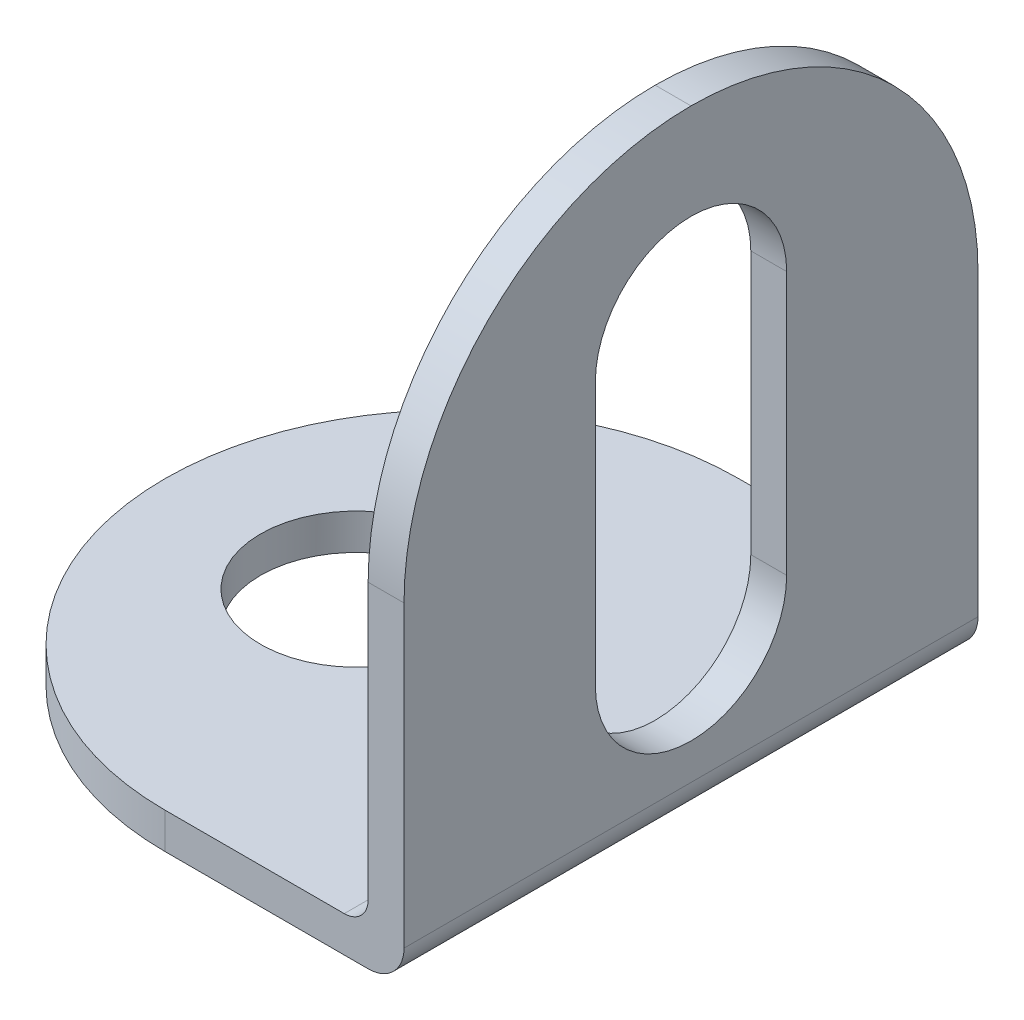
SolidWorks part; units mm, degrees
ref_plane "Piano frontale" through (0, 0, 0) normal (0, 0, 1) x (1, 0, 0)
ref_plane "Piano superiore" through (0, 0, 0) normal (0, 1, 0) x (1, 0, 0)
ref_plane "Piano destro" through (0, 0, 0) normal (1, 0, 0) x (0, 0, -1)
sketch "Schizzo1" plane through (0, 0, 0) normal (0, 0, 1) x (1, 0, 0)
  line L0 (0, 13) -> (0, 0)
  line L1 (0, 0) -> (-11, 0)
  dimension "D1" = 13
  dimension "D2" = 11
extrude "Estrusione-Sottile1" add sketch "Schizzo1" along normal mid plane 12 thin contours L0 L1 thin type one direction wall 0.75
fillet "Raccordo3" radius 6 4 edges at (-11, 0.375, 6) (-11, 0.375, -6) (-0.375, 13, -6) (-0.375, 13, 6)
sketch "Schizzo4" plane through (0, 0.75, 0) normal (0, 1, 0) x (1, 0, 0)
  circle A2 centre (-7, 0) radius 2
  point P0 (-5.8105, -0.1666)
  dimension "D1" = 4
  dimension "D2" = 4
extrude "Taglio-Estrusione1" cut sketch "Schizzo4" against normal up to surface (0.75 mm away) up to face at (-4.6971, 0, 0)
sketch "Schizzo5" plane through (-0.75, 0, 0) normal (-1, 0, 0) x (0, 0, 1)
  line L0 (0, 9) -> (0, 3.5) construction
  line L1 (2, 9) -> (2, 3.5)
  line L2 (-2, 9) -> (-2, 3.5)
  arc A0 (2, 9) -> (-2, 9) centre (0, 9) ccw
  arc A1 (-2, 3.5) -> (2, 3.5) centre (0, 3.5) ccw
  point P3 (0, 6.25)
  point P9 (0, 11)
  point P10 (0, 4.3327)
  point P11 (0, 1.5)
  dimension "D1" = 2
  dimension "D2" = 2
  dimension "D3" = 1.5
fillet "Raccordo1" radius 0.75 1 edges at (0, 0, 0)
fillet "Raccordo2" radius 0.5 1 edges at (-0.75, 0.75, 0)
extrude "Taglio-Estrusione2" cut sketch "Schizzo5" against normal up to surface (0.75 mm away) up to face at (0, 6.1971, 0)
